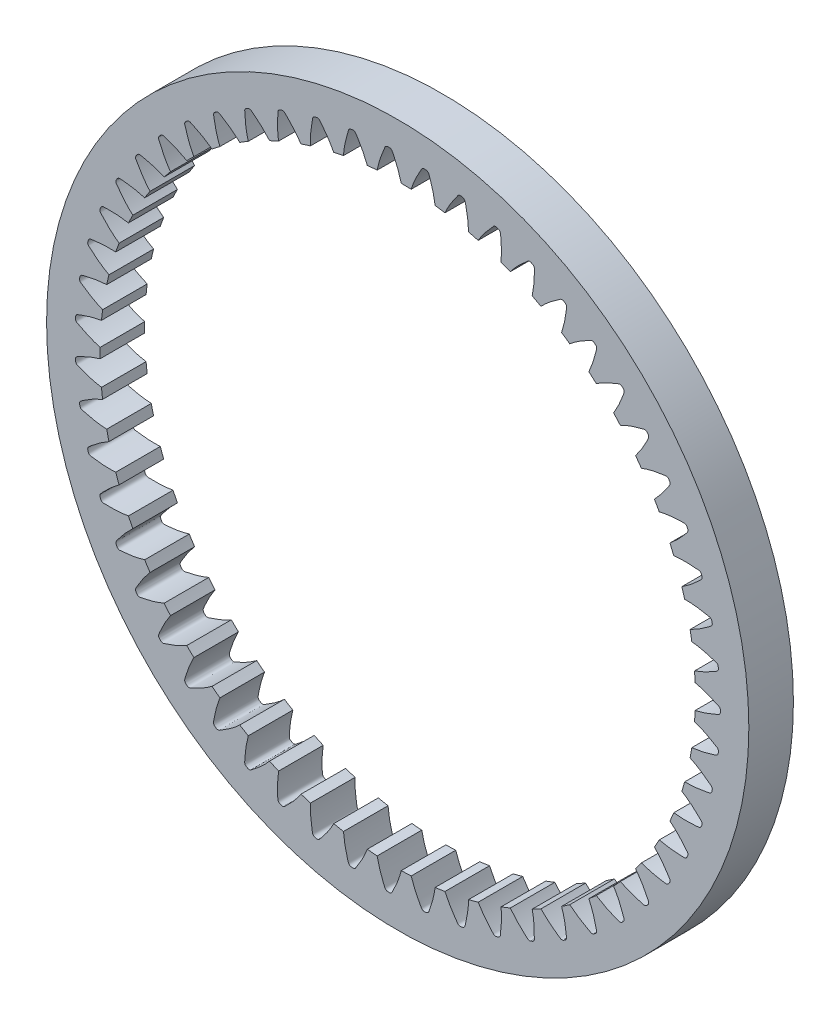
SolidWorks part; units mm, degrees
ref_plane "Front Plane" through (0, 0, 0) normal (0, 0, 1) x (1, 0, 0)
ref_plane "Top Plane" through (0, 0, 0) normal (0, 1, 0) x (1, 0, 0)
ref_plane "Right Plane" through (0, 0, 0) normal (1, 0, 0) x (0, 0, -1)
ref_axis "Axis1" through (0, 0, 55) along (0, 0, -1)
sketch "SketchRevolveSpurGear" plane through (0, 0, 0) normal (1, 0, 0) x (0, 0, -1)
  line L0 (0, 0) -> (1, 0) construction
  line L1 (-2, 26.7) -> (-2, 31.5)
  line L2 (-2, 31.5) -> (2, 31.5)
  line L3 (2, 31.5) -> (2, 26.7)
  line L4 (2, 26.7) -> (-2, 26.7)
  dimension "Side1" = 2
  dimension "OutsideRadius" = 31.5
  dimension "Side2" = 2
  dimension "MinorDiameter" = 53.4
revolve "SpurGear" add sketch "SketchRevolveSpurGear" angle 360 about L0
sketch "SketchToothSpurGear" plane through (0, 0, 0) normal (0, 0, 1) x (1, 0, 0)
  arc A0 (26.6611, -1.0844) -> (26.6611, 1.0844) centre (0, 0) ccw
  spline S0 degree 3 poles (26.6611, 1.0844) (26.7713, 1.0607) (26.9424, 1.0195) (27.1776, 0.9545) (27.373, 0.8955) (27.5803, 0.8276) (27.7992, 0.7503) (28.0292, 0.6628) (28.2705, 0.5652) (28.5213, 0.4543) (28.7068, 0.3744) (28.8169, 0.3155) (28.8506, 0.2891) (28.8801, 0.2588) (28.905, 0.2247) (28.9248, 0.1873) (28.9441, 0.1349) (28.9506, 0.0821) (28.9499, 0.0327) (28.9501, 0) (28.9499, -0.0327) (28.9506, -0.0821) (28.9441, -0.1349) (28.9248, -0.1873) (28.905, -0.2247) (28.8801, -0.2588) (28.8506, -0.2891) (28.8169, -0.3155) (28.7068, -0.3744) (28.5213, -0.4543) (28.2705, -0.5652) (28.0292, -0.6628) (27.7992, -0.7503) (27.5803, -0.8276) (27.373, -0.8955) (27.1776, -0.9545) (26.9424, -1.0195) (26.7713, -1.0607) (26.6611, -1.0844) knots 0 0 0 0 0.063683 0.099491 0.137943 0.17904 0.222781 0.269167 0.318197 0.369871 0.42419 0.432384 0.440322 0.448261 0.456199 0.464138 0.472077 0.487661 0.493831 0.5 0.506169 0.512339 0.527923 0.535862 0.543801 0.551739 0.559678 0.567616 0.57581 0.630129 0.681803 0.730833 0.777219 0.82096 0.862057 0.900509 0.936317 1 1 1 1
extrude "ToothExtrudeCutSpurGear" cut sketch "SketchToothSpurGear" against normal blind 2 and the other way blind 2
pattern_circular "PatternSpurGear" count 55 every 6.545 about axis through (0, 0, 55) along (0, 0, -1) of "ToothExtrudeCutSpurGear"
sketch "AuxiliarySketchSpurGear" plane through (0, 0, 0) normal (0, 0, 1) x (1, 0, 0)
  circle A0 centre (0, 0) radius 27.5 construction
  circle A1 centre (0, 0) radius 25.8415 construction
  circle A2 centre (0, 0) radius 28.95 construction
  circle A3 centre (0, 0) radius 26.7 construction
  dimension "PitchDiameter" = 55
  dimension "BaseDiameter" = 51.6831
  dimension "MajorDiameter" = 57.9
  dimension "MinorDiameter" = 53.4
sketch "Sketch4" plane through (0, 0, 0) normal (0, 0, 1) x (1, 0, 0)
  circle A0 centre (0, 0) radius 30.5
  circle A1 centre (0, 0) radius 59.7587
  dimension "D1" = 61
extrude "Cut-Extrude2" [suppressed] cut sketch "Sketch4" against normal through all both and the other way through all
